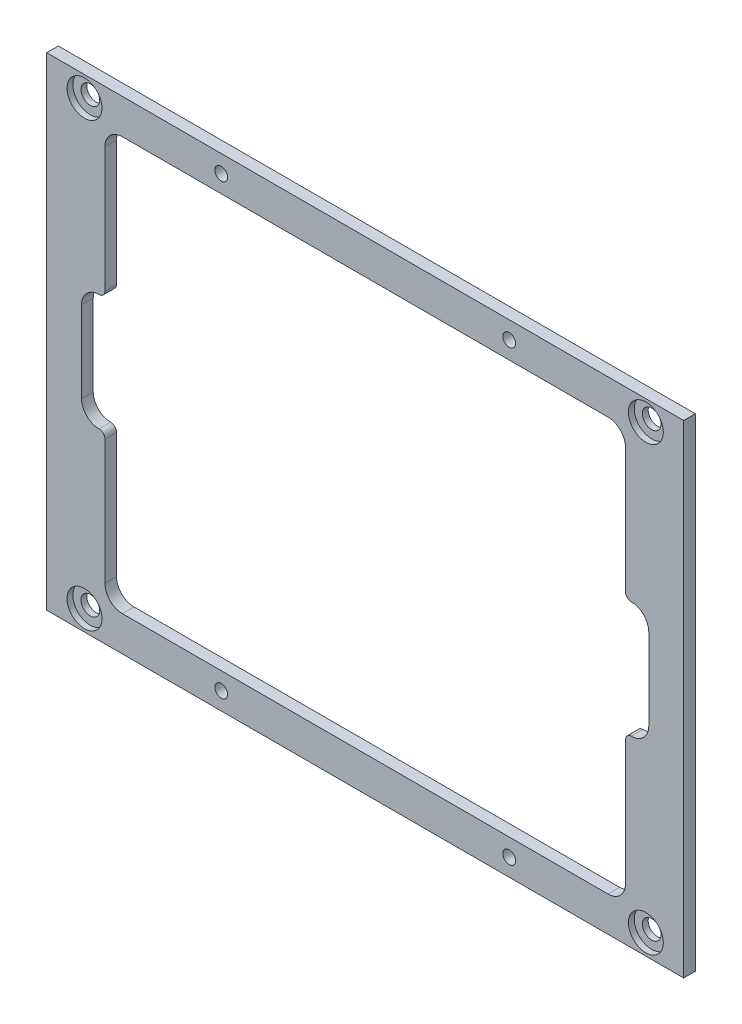
SolidWorks part; units mm, degrees
ref_plane "Front Plane" through (0, 0, 0) normal (0, 0, 1) x (1, 0, 0)
ref_plane "Top Plane" through (0, 0, 0) normal (0, 1, 0) x (1, 0, 0)
ref_plane "Right Plane" through (0, 0, 0) normal (1, 0, 0) x (0, 0, -1)
sketch "Sketch1" plane through (0, 0, 7.4347) normal (0, 0, 1) x (1, 0, 0)
  line L0 (-55.4936, 6.4519) -> (-55.4936, 3.4519) construction
  line L1 (-55.4936, 3.4519) -> (54.0064, 3.4519)
  line L2 (-55.4936, 3.4519) -> (-55.4936, 86.4519)
  line L3 (-55.4936, 86.4519) -> (54.0064, 86.4519)
  line L4 (54.0064, 3.4519) -> (54.0064, 86.4519)
  line L5 (55.0064, 3.4519) -> (-56.4936, 3.4519) construction
  line L6 (-51.4936, 3.4519) -> (-51.4936, 86.4519) construction
  line L7 (-42.4936, 80.4519) -> (41.0064, 80.4519)
  line L8 (-45.4936, 77.4519) -> (-45.4936, 54.9519)
  line L9 (-42.4936, 9.4519) -> (41.0064, 9.4519)
  line L10 (44.0064, 77.4519) -> (44.0064, 54.9519)
  line L11 (54.0064, 44.9519) -> (44.0064, 44.9519) construction
  line L12 (44.0064, 54.9519) -> (48.0064, 54.9519)
  line L13 (-45.4936, 54.9519) -> (-49.4936, 54.9519)
  line L14 (44.0064, 34.9519) -> (48.0064, 34.9519)
  line L15 (48.0064, 54.9519) -> (48.0064, 44.9519)
  line L16 (48.0064, 44.9519) -> (48.0064, 34.9519)
  line L17 (44.0064, 34.9519) -> (44.0064, 12.4519)
  line L18 (-49.4936, 54.9519) -> (-49.4936, 34.9519)
  line L19 (-49.4936, 34.9519) -> (-45.4936, 34.9519)
  line L20 (-45.4936, 34.9519) -> (-45.4936, 12.4519)
  arc A0 (-45.4936, 12.4519) -> (-42.4936, 9.4519) centre (-42.4936, 12.4519) ccw
  arc A1 (41.0064, 9.4519) -> (44.0064, 12.4519) centre (41.0064, 12.4519) ccw
  arc A2 (41.0064, 80.4519) -> (44.0064, 77.4519) centre (41.0064, 77.4519) cw
  arc A3 (-42.4936, 80.4519) -> (-45.4936, 77.4519) centre (-42.4936, 77.4519) ccw
  dimension "D7" = 3
  dimension "D1" = 109.5
  dimension "D2" = 83
  dimension "D3" = 6
  dimension "D4" = 6
  dimension "D5" = 6
  dimension "D6" = 6
  dimension "D8" = 10
  dimension "D9" = 10
  dimension "D10" = 4
  dimension "D11" = 4
  dimension "D12" = 20
  dimension "D13" = 31.5
  dimension "D14" = 31.5
extrude "Boss-Extrude1" add sketch "Sketch1" along normal blind 2
hole_wizard "Ø3.2 (3.2) Diameter Hole1" positions "Sketch7" profile "Sketch6" hole size "Ø3.2" standard "Ansi Metric" end condition up to next
sketch "Sketch7" plane through (0, 0, 9.4347) normal (0, 0, 1) x (1, 0, 0)
  line L0 (-55.4936, 3.4519) -> (54.0064, 3.4519) construction
  line L1 (-55.4936, 86.4519) -> (-55.4936, 3.4519) construction
  line L2 (54.0064, 86.4519) -> (-55.4936, 86.4519) construction
  line L3 (54.0064, 3.4519) -> (54.0064, 86.4519) construction
  point P0 (-48.9936, 6.9519)
  point P7 (-48.9936, 82.9519)
  point P9 (47.5064, 82.9519)
  point P11 (47.5064, 6.9519)
  dimension "D1" = 3.5
  dimension "D2" = 6.5
  dimension "D3" = 6.5
  dimension "D4" = 3.5
  dimension "D5" = 3.5
  dimension "D6" = 6.5
  dimension "D7" = 6.5
  dimension "D8" = 3.5
sketch "Sketch6" plane through (-48.9936, 6.9519, 9.4347) normal (1, 0, 0) x (0, -1, 0)
  line L0 (0, 0) -> (0, 2)
  line L1 (0, 2) -> (1.6, 2)
  line L2 (1.6, 2) -> (1.6, 0)
  line L5 (1.6, 0) -> (0, 0)
  line L11 (0, -6.35) -> (0, 107.95) construction
  dimension "Thru Hole Dia." = 3.2
  dimension "Thru Hole Depth" = 2
hole_wizard "Ø2.2 (2.2) Diameter Hole1" positions "3DSketch4" profile "Sketch11" hole size "Ø2.2" standard "Ansi Metric" end condition up to next
sketch3d "3DSketch4"
  line L0 (54.0064, 86.4519, 9.4347) -> (-55.4936, 86.4519, 9.4347) construction
  line L1 (-55.4936, 86.4519, 9.4347) -> (-55.4936, 3.4519, 9.4347) construction
  line L2 (54.0064, 3.4519, 9.4347) -> (54.0064, 86.4519, 9.4347) construction
  line L3 (-55.4936, 3.4519, 9.4347) -> (54.0064, 3.4519, 9.4347) construction
  point P0 (-25.4936, 83.4519, 9.4347)
  point P2 (24.0064, 83.4519, 9.4347)
  point P4 (24.0064, 6.4519, 9.4347)
  point P6 (-25.4936, 6.4519, 9.4347)
  dimension "D1" = 3
  dimension "D2" = 30
  dimension "D3" = 3
  dimension "D4" = 30
  dimension "D5" = 3
  dimension "D6" = 30
  dimension "D7" = 3
  dimension "D8" = 30
sketch "Sketch11" plane through (-25.4936, 83.4519, 9.4347) normal (1, 0, 0) x (0, -1, 0)
  line L0 (0, 0) -> (0, 2)
  line L1 (0, 2) -> (1.1, 2)
  line L2 (1.1, 2) -> (1.1, 0)
  line L5 (1.1, 0) -> (0, 0)
  line L11 (0, -6.35) -> (0, 107.95) construction
  dimension "Thru Hole Dia." = 2.2
  dimension "Thru Hole Depth" = 2
sketch "Sketch12" plane through (0, 0, 9.4347) normal (0, 0, 1) x (1, 0, 0)
  circle A0 centre (-48.9936, 82.9519) radius 3
  circle A1 centre (47.5064, 82.9519) radius 3
  circle A2 centre (47.5064, 6.9519) radius 3
  circle A3 centre (-48.9936, 6.9519) radius 3
  dimension "D1" = 6
  dimension "D2" = 6
  dimension "D3" = 6
  dimension "D4" = 6
extrude "Cut-Extrude1" cut sketch "Sketch12" against normal blind 1
fillet "Fillet1" radius 3 4 edges at (48.0064, 34.9519, 8.4347) (48.0064, 54.9519, 8.4347) (-49.4936, 34.9519, 8.4347) (-49.4936, 54.9519, 8.4347)
fillet "Fillet2" radius 1 4 edges at (44.0064, 34.9519, 8.4347) (44.0064, 54.9519, 8.4347) (-45.4936, 34.9519, 8.4347) (-45.4936, 54.9519, 8.4347)
